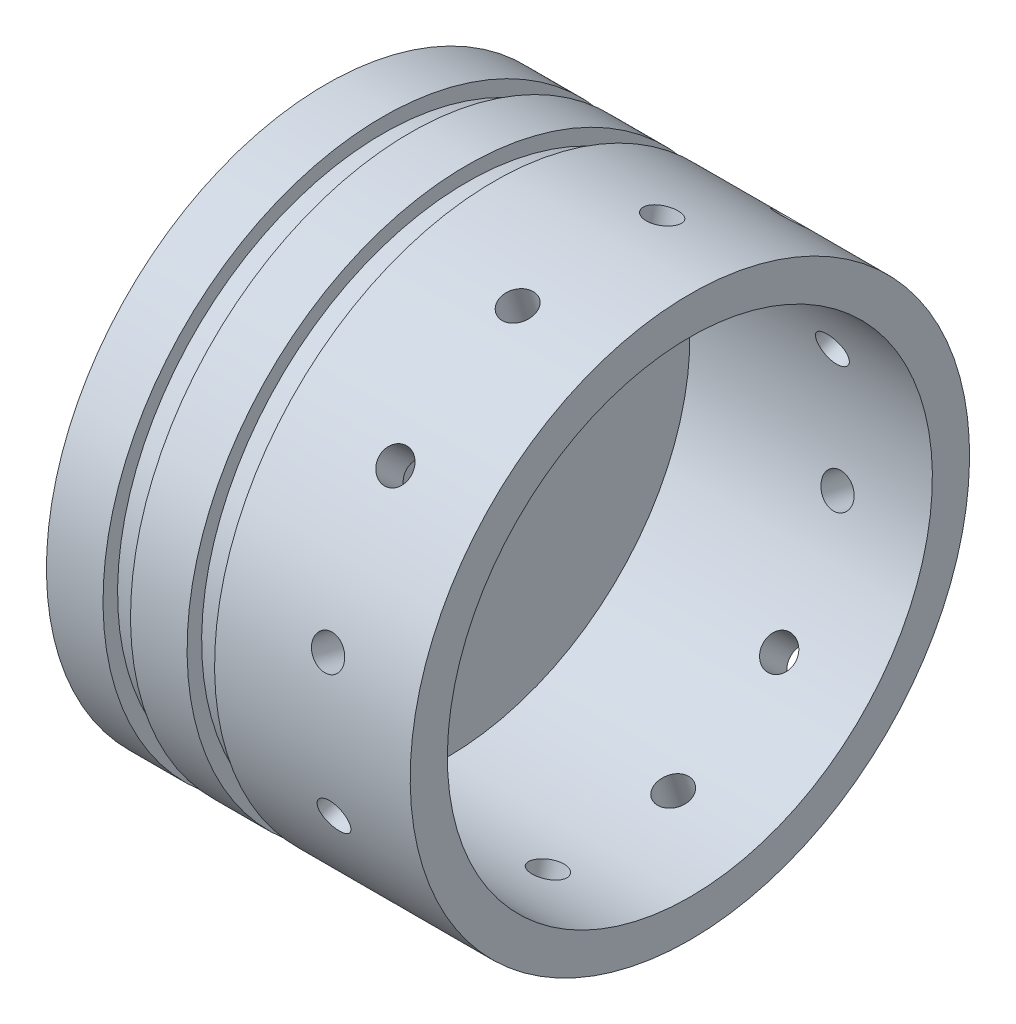
SolidWorks part; units mm, degrees
ref_plane "Front Plane" through (0, 0, 0) normal (0, 0, 1) x (1, 0, 0)
ref_plane "Top Plane" through (0, 0, 0) normal (0, 1, 0) x (1, 0, 0)
ref_plane "Right Plane" through (0, 0, 0) normal (1, 0, 0) x (0, 0, -1)
sketch "Sketch1" plane through (0, 0, 0) normal (0, 0, 1) x (1, 0, 0)
  line L0 (13.208, 43.942) -> (22.098, 43.942)
  line L2 (0, 5.5562) -> (0, 43.942)
  line L3 (0, 43.942) -> (8.89, 43.942)
  line L4 (57.15, 38.1) -> (57.15, 43.942)
  line L7 (57.15, 38.1) -> (19.05, 38.1)
  line L8 (19.05, 5.5563) -> (19.05, 38.1)
  line L10 (8.89, 43.942) -> (8.89, 41.656)
  line L11 (8.89, 41.656) -> (13.208, 41.656)
  line L12 (13.208, 43.942) -> (13.208, 41.656)
  line L14 (22.098, 43.942) -> (22.098, 41.656)
  line L15 (22.098, 41.656) -> (26.416, 41.656)
  line L16 (26.416, 43.942) -> (26.416, 41.656)
  line L17 (26.416, 43.942) -> (57.15, 43.942)
  line L18 (0, 5.5562) -> (19.05, 5.5563)
  line L19 (0, 0) -> (19.05, 0) construction
  dimension "D1" = 43.942
  dimension "D2" = 57.15
  dimension "D3" = 19.05
  dimension "D4" = 38.1
  dimension "D5" = 38.1
  dimension "D6" = 4.318
  dimension "D7" = 8.89
  dimension "D8" = 4.318
  dimension "D9" = 8.89
  dimension "D10" = 41.656
  dimension "D11" = 5.5562
revolve "Revolve1" add sketch "Sketch1" angle 360 about L19
thread "Thread1" pitch 1.8143 method cut profile "Thread Profile2" start angle 0, offset 0, length 0, pitch 1.8143, diameter 11.1125
ref_plane "Plane2" through (19.05, 0, 5.5563) normal (0, -1, 0) x (0, 0, 1)
sketch "Thread Profile2" plane through (19.05, 0, 5.5563) normal (0, -1, 0) x (0, 0, 1)
  line L0 (0, 0) -> (0, 1.8143) construction
  line L1 (0, 0) -> (0.982, 0.567)
  line L2 (0.982, 0.567) -> (0.982, 0.7937)
  line L3 (0.982, 0.7937) -> (0, 1.3607)
  line L4 (0.982, 0.6804) -> (0, 0.6804) construction
  line L11 (0, 0) -> (0, 1.3607)
  point P2 (0, 0)
  dimension "Pitch" = 1.8143
  dimension "Profile_Angle" = 60
  dimension "Profile_Land" = 0.2268
  dimension "Profile_Height" = 0.982
hole_wizard "1/4-20 Tapped Hole1" positions "3DSketch1" profile "Sketch2" tap size "1/4-20" standard "ANSI Inch"
sketch3d "3DSketch1"
  point P0 (43.18, 41.9439, 13.0999)
  dimension "D1" = 13.97
sketch "Sketch2" plane through (43.18, 41.9439, 13.0999) normal (1, 0, 0) x (0, -0.2981, 0.9545)
  line L0 (0, 0) -> (0, 45.4748)
  line L1 (0, 45.4748) -> (2.5527, 43.941)
  line L2 (2.5527, 43.941) -> (2.5527, 0)
  line L5 (2.5527, 0) -> (0, 0)
  line L10 (0, 45.4748) -> (-2.5527, 43.941) construction
  line L11 (0, -6.35) -> (0, 107.95) construction
  dimension "Tap Drill Dia." = 5.1054
  dimension "Tap Drill Depth" = 43.941
  dimension "Drill Angle" = 118
pattern_circular "CirPattern1" count 12 over 360 about axis through (57.15, 0, 0) along (-1, 0, 0) of "1/4-20 Tapped Hole1"
